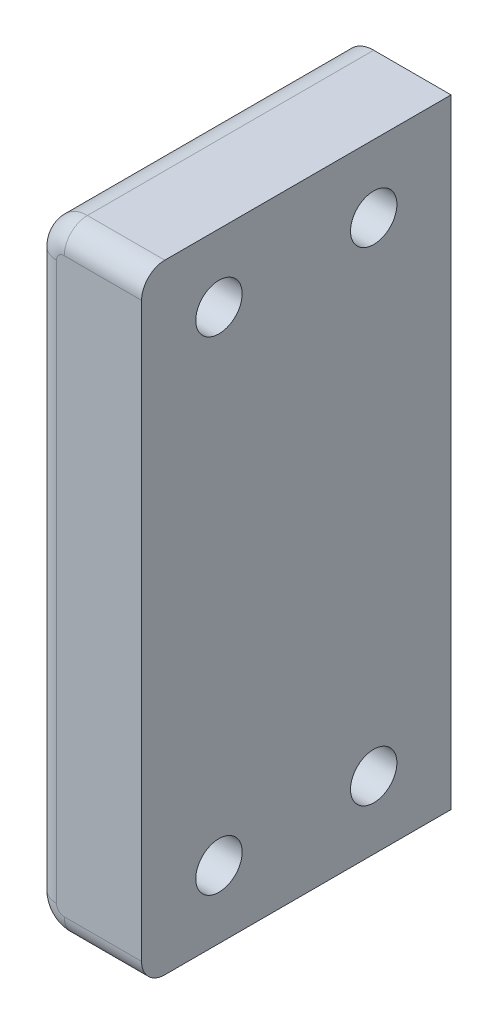
SolidWorks part; units mm, degrees
ref_plane "Front Plane" through (0, 0, 0) normal (0, 0, 1) x (1, 0, 0)
ref_plane "Top Plane" through (0, 0, 0) normal (0, 1, 0) x (1, 0, 0)
ref_plane "Right Plane" through (0, 0, 0) normal (1, 0, 0) x (0, 0, -1)
sketch "Sketch2" plane through (0, 0, 0) normal (0, 0, 1) x (1, 0, 0)
  line L0 (-148, -68) -> (-132, -68) construction
  line L1 (-148, -28) -> (-153, -28)
  line L2 (-148, -28) -> (-148, -68)
  line L3 (-148, -68) -> (-153, -68)
  line L4 (-155, -30) -> (-155, -66)
  arc A0 (-153, -68) -> (-155, -66) centre (-153, -66) cw
  arc A1 (-153, -28) -> (-155, -30) centre (-153, -30) ccw
  point P10 (-155, -68)
extrude "Boss-Extrude1" add sketch "Sketch2" along normal up to surface (20 mm away)
sketch "Sketch3" plane through (-148, 0, 0) normal (1, 0, 0) x (0, 0, -1)
  circle A0 centre (-15, -63.625) radius 1.5
  circle A1 centre (-5, -63.625) radius 1.5
  circle A2 centre (-5, -32.375) radius 1.5
  circle A3 centre (-15, -32.375) radius 1.5
extrude "Cut-Extrude1" cut sketch "Sketch3" against normal blind 10
fillet "Fillet1" radius 1.5 5 edges at (-150.5, -68, 20) (-154.4142, -67.4142, 20) (-155, -48, 20) (-154.4142, -28.5858, 20) (-150.5, -28, 20)
